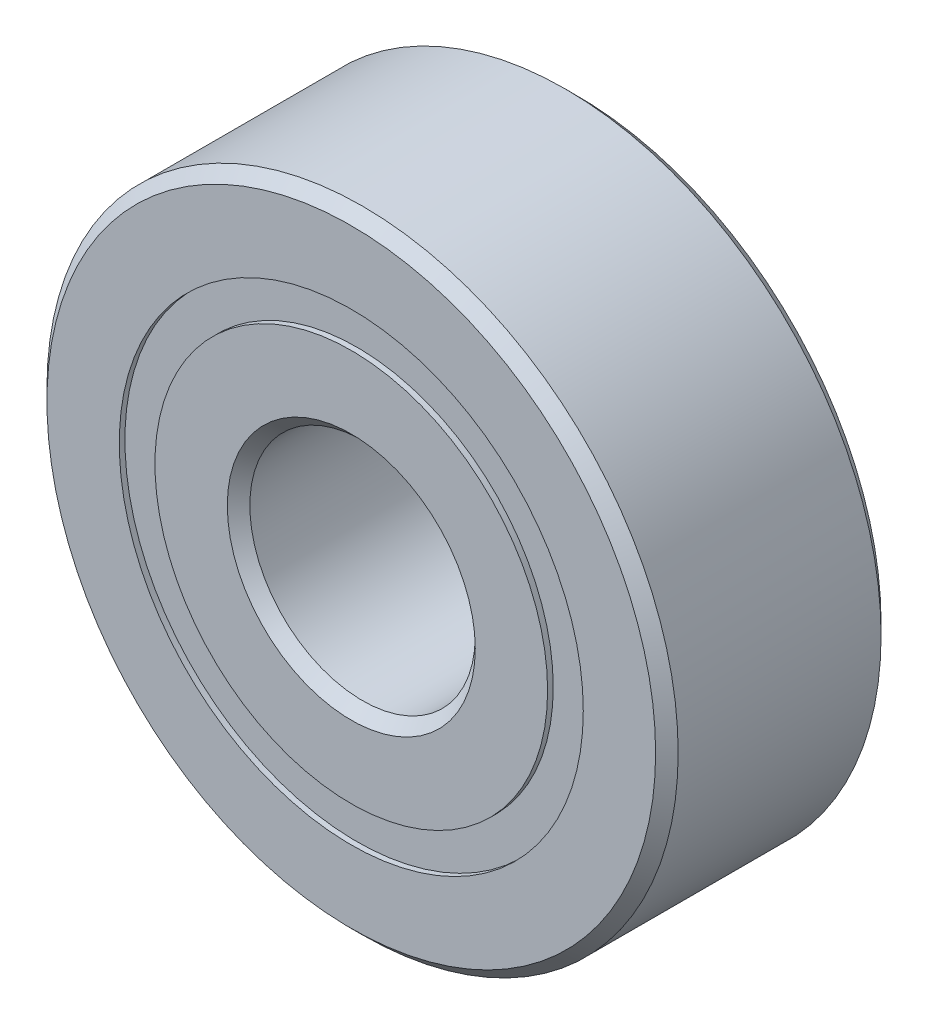
SolidWorks part; units mm, degrees
ref_plane "Front Plane" through (0, 0, 0) normal (0, 0, 1) x (1, 0, 0)
ref_plane "Top Plane" through (0, 0, 0) normal (0, 1, 0) x (1, 0, 0)
ref_plane "Right Plane" through (0, 0, 0) normal (1, 0, 0) x (0, 0, -1)
sketch "Sketch1" plane through (0, 0, 0) normal (1, 0, 0) x (0, 0, -1)
  line L0 (-2.5, 0) -> (2.5, 0) construction
  line L1 (0, 7) -> (0, -7) construction
  line L2 (2.25, 7) -> (-2.25, 7)
  line L3 (-2.25, 7) -> (-2.5, 6.75)
  line L4 (-2.5, 6.75) -> (-2.5, 5.1456)
  line L5 (-2.5, 5.1456) -> (-1.1111, 5.1456)
  line L6 (2.5, 5.1456) -> (1.1111, 5.1456)
  line L7 (2.5, 6.75) -> (2.5, 5.1456)
  line L8 (2.25, 7) -> (2.5, 6.75)
  line L9 (0, 7) -> (0, 4.75) construction
  line L10 (0, 4.75) -> (0, 2.5) construction
  arc A0 (-1.1111, 5.1456) -> (1.1111, 5.1456) centre (0, 4.75) cw
  point P14 (0, 2.5)
  dimension "D3" = 2.2222
  dimension "D1" = 45
  dimension "Width" = 5
  dimension "OD" = 14
  dimension "D2" = 0.25
  dimension "Shaft Dia" = 5
  dimension "D4" = 0.3956
revolve "Revolve1" add sketch "Sketch1" angle 360 about L0
sketch "Sketch3" plane through (0, 0, 0) normal (1, 0, 0) x (0, 0, -1)
  line L0 (-2.5, 4.3544) -> (-1.1111, 4.3544)
  line L1 (0, 7) -> (0, -7) construction
  line L2 (-2.5, 6.75) -> (-2.5, 5.1456) construction
  line L3 (-2.5, 4.3544) -> (-2.5, 2.75)
  line L4 (-2.25, 7) -> (-2.5, 6.75) construction
  line L5 (-2.5, 2.75) -> (-2.25, 2.5)
  line L6 (-2.25, 2.5) -> (2.25, 2.5)
  line L7 (2.25, 7) -> (2.25, -7) construction
  line L8 (2.25, 2.5) -> (2.5, 2.75)
  line L9 (2.5, -6.75) -> (2.5, 6.75) construction
  line L10 (2.5, 2.75) -> (2.5, 4.3544)
  line L11 (2.5, 4.3544) -> (1.1111, 4.3544)
  line L13 (2.25, 7) -> (2.5, 6.75) construction
  arc A0 (1.1111, 5.1456) -> (-1.1111, 5.1456) centre (0, 4.75) ccw construction
  arc A1 (1.1111, 4.3544) -> (-1.1111, 4.3544) centre (0, 4.75) cw
revolve "Revolve3" add sketch "Sketch3" angle 360 about L0
sketch "Sketch4" plane through (0, 0, 0) normal (1, 0, 0) x (0, 0, -1)
  line L0 (-1.1794, 4.75) -> (1.1794, 4.75)
  arc A2 (-1.1794, 4.75) -> (1.1794, 4.75) centre (0, 4.75) cw
  arc A3 (1.1111, 5.1456) -> (-1.1111, 5.1456) centre (0, 4.75) ccw construction
revolve "Revolve4" add sketch "Sketch4" angle 360 about L0
ref_axis "Axis1" through (0, 0, -2.5) along (0, 0, 1)
pattern_circular "CirPattern1" count 12 every 30 about axis through (0, 0, -2.5) along (0, 0, 1) of bodies 104
sketch "Sketch5" plane through (0, 0, 0) normal (1, 0, 0) x (0, 0, -1)
  line L0 (-2.5, 5.1456) -> (-1.1111, 5.1456) construction
  line L1 (-2.375, 5.1456) -> (-1.1794, 5.1456)
  line L2 (-2.375, 5.1456) -> (-2.375, 4.3544)
  line L3 (-2.375, 4.3544) -> (-1.1794, 4.3544)
  line L4 (-1.1794, 5.1456) -> (-1.1794, 4.3544)
  line L5 (-2.5, 4.3544) -> (-1.1111, 4.3544) construction
  line L6 (2.5, 5.1456) -> (1.1111, 5.1456) construction
  line L7 (2.375, 5.1456) -> (1.1794, 5.1456)
  line L8 (2.375, 5.1456) -> (2.375, 4.3544)
  line L9 (2.375, 4.3544) -> (1.1794, 4.3544)
  line L10 (1.1794, 5.1456) -> (1.1794, 4.3544)
  line L11 (2.5, 4.3544) -> (1.1111, 4.3544) construction
  line L12 (-2.25, 7) -> (-2.5, 6.75) construction
  point P18 (-2.375, 6.875)
revolve "Revolve5" add sketch "Sketch5" angle 360 about L0
sketch "Sketch6" plane through (0, 0, 0) normal (1, 0, 0) x (0, 0, -1)
  line L0 (2.5, 0) -> (-2.5, 0) construction
  line L1 (2.5, 5.1456) -> (1.7126, 5.1456)
  line L2 (2.5, 5.1456) -> (2.5, 6.9469)
  line L3 (2.5, 6.9469) -> (1.7126, 6.9469)
  line L4 (1.7126, 5.1456) -> (1.7126, 6.9469)
  dimension "Th" = 0.7874
  dimension "Flange OD" = 13.8938
revolve "Revolve6" [suppressed] add sketch "Sketch6" angle 360 about L0
equation "\"D2@Sketch1\" = \"Width@Sketch1\"*.05"
equation "\"D3@Sketch1\" = \"Width@Sketch1\"/2.25"
equation "\"D4@Sketch1\" = (((\"OD@Sketch1\"-\"Width@Sketch1\")/2)/3.25)/3.5"
equation "\"D2@CirPattern1\" = 360/\"Balls@CirPattern1\""
